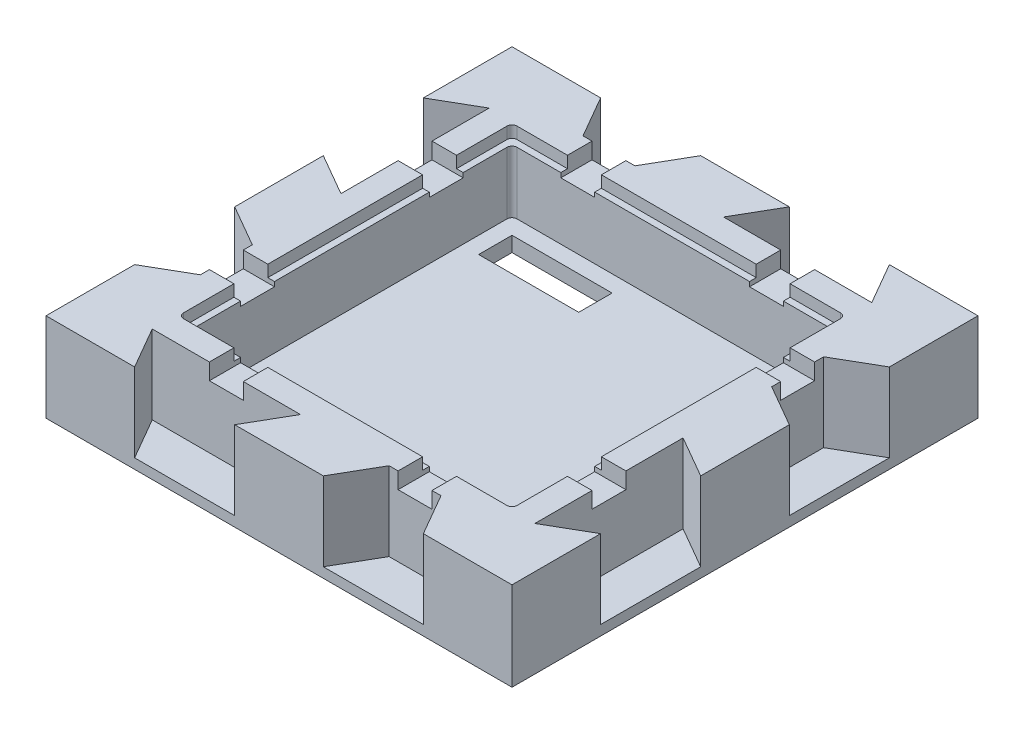
SolidWorks part; units mm, degrees
material "Macor"
ref_plane "Front Plane" through (0, 0, 0) normal (0, 0, 1) x (1, 0, 0)
ref_plane "Top Plane" through (0, 0, 0) normal (0, 1, 0) x (1, 0, 0)
ref_plane "Right Plane" through (0, 0, 0) normal (1, 0, 0) x (0, 0, -1)
sketch "Sketch1" plane through (0, 0, 0) normal (0, 1, 0) x (1, 0, 0)
  line L1 (-69.85, -69.85) -> (69.85, -69.85)
  line L2 (-69.85, -69.85) -> (-69.85, 69.85)
  line L3 (-69.85, 69.85) -> (69.85, 69.85)
  line L4 (69.85, -69.85) -> (69.85, 69.85)
  line L5 (-69.85, -69.85) -> (69.85, 69.85) construction
  line L6 (-69.85, 69.85) -> (69.85, -69.85) construction
  point P0 (0, 0)
  dimension "D1" = 139.7
extrude "Boss-Extrude1" add sketch "Sketch1" along normal mid plane 26.9 contours L2 L1 L4 L3
sketch "Sketch2" plane through (0, 13.45, 0) normal (0, 1, 0) x (1, 0, 0)
  line L0 (69.85, -69.85) -> (69.85, 69.85) construction
  line L1 (-69.85, -69.85) -> (69.85, -69.85)
  line L2 (-69.85, -69.85) -> (-69.85, 69.85)
  line L3 (-69.85, 69.85) -> (69.85, 69.85)
  line L4 (69.85, -69.85) -> (69.85, 69.85)
  line L5 (-69.85, -69.85) -> (69.85, 69.85) construction
  line L6 (-69.85, 69.85) -> (69.85, -69.85) construction
  point P0 (0, 0)
  dimension "D1" = 0
extrude "Cut-Extrude1" cut sketch "Sketch2" against normal offset from surface (0.3 mm away) 0.3 up to face at (0, 13.45, 0)
sketch "Sketch4" plane through (0, 13.15, 0) normal (0, 1, 0) x (1, 0, 0)
  line L0 (-43.2833, -69.85) -> (-50.5002, -57.35)
  line L2 (-50.5002, -57.35) -> (-6.0665, -57.35)
  line L3 (-6.0665, -57.35) -> (-13.2833, -69.85)
  line L4 (-13.2833, -69.85) -> (-43.2833, -69.85)
  line L5 (43.2833, -69.85) -> (36.0665, -57.35)
  line L24 (43.2833, -69.85) -> (13.2833, -69.85)
  line L25 (-69.85, -69.85) -> (-43.2833, -69.85) construction
  line L26 (-13.2833, -69.85) -> (13.2833, -69.85) construction
  line L27 (43.2833, -69.85) -> (69.85, -69.85) construction
  line L28 (36.0665, -57.35) -> (20.5002, -57.35)
  line L30 (13.2833, -69.85) -> (20.5002, -57.35)
  line L31 (-69.85, 69.85) -> (-69.85, -69.85) construction
  line L32 (69.85, -69.85) -> (69.85, 69.85) construction
  line L33 (-69.85, -69.85) -> (69.85, -69.85) construction
  dimension "D2" = 30
  dimension "D1" = 60
  dimension "D3" = 12.5
  dimension "D4" = 60
extrude "Cut-Extrude2" cut sketch "Sketch4" against normal offset from surface 3 and the other way through all up to face at (0, -13.45, 0)
sketch "Sketch18" plane through (0, 0, 57.35) normal (0, 0, 1) x (1, 0, 0)
  line L1 (0, -55) -> (0, 55) construction
  line L3 (23.2033, 13.15) -> (23.2033, 8.275)
  line L4 (23.2033, 8.275) -> (33.3633, 8.275)
  line L5 (33.3633, 13.15) -> (33.3633, 8.275)
  line L6 (-23.2033, 13.15) -> (-33.3633, 13.15)
  line L7 (-33.3633, 13.15) -> (-33.3633, 8.275)
  line L8 (-23.2033, 13.15) -> (-23.2033, 8.275)
  line L9 (-23.2033, 8.275) -> (-33.3633, 8.275)
  line L10 (23.2033, 13.15) -> (33.3633, 13.15)
  line L11 (20.5002, 13.15) -> (36.0665, 13.15) construction
  point P7 (28.2833, 13.15)
  point P14 (28.2833, 13.15)
  dimension "D1" = 10.16
  dimension "D2" = 4.875
extrude "Cut-Extrude6" cut sketch "Sketch18" against normal blind 20
ref_axis "Axis1" through (0, 29.6009, 0) along (0, -1, 0)
pattern_circular "CirPattern1" count 4 over 360 about axis through (0, 29.6009, 0) along (0, -1, 0) of "Cut-Extrude2", "Cut-Extrude6"
sketch "Sketch19" plane through (0, 13.15, 0) normal (0, 1, 0) x (1, 0, 0)
  line L1 (-50, -50) -> (50, -50)
  line L2 (-50, -50) -> (-50, 50)
  line L3 (-50, 50) -> (50, 50)
  line L4 (50, -50) -> (50, 50)
  line L5 (-50, -50) -> (50, 50) construction
  line L6 (-50, 50) -> (50, -50) construction
  point P0 (0, 0)
  dimension "D1" = 100
extrude "Cut-Extrude8" cut sketch "Sketch19" against normal blind 3.5
sketch "Sketch20" plane through (0, 9.65, 0) normal (0, 1, 0) x (1, 0, 0)
  line L1 (-48, -48) -> (48, -48)
  line L2 (-48, -48) -> (-48, 48)
  line L3 (-48, 48) -> (48, 48)
  line L4 (48, -48) -> (48, 48)
  line L5 (-48, -48) -> (48, 48) construction
  line L6 (-48, 48) -> (48, -48) construction
  point P0 (0, 0)
  dimension "D1" = 96
extrude "Cut-Extrude9" cut sketch "Sketch20" against normal blind 18.6
sketch "Sketch21" plane through (0, -8.95, 0) normal (0, 1, 0) x (1, 0, 0)
  line L0 (-48, 48) -> (-48, -48) construction
  line L1 (-13, 33) -> (-43, 33)
  line L2 (-13, 33) -> (-13, 43)
  line L3 (-13, 43) -> (-43, 43)
  line L4 (-43, 33) -> (-43, 43)
  line L5 (48, 48) -> (-48, 48) construction
  dimension "D1" = 30
  dimension "D2" = 10
  dimension "D3" = 5
  dimension "D4" = 5
extrude "Cut-Extrude10" cut sketch "Sketch21" against normal through all
fillet "Fillet2" radius 1.5 8 edges at (-50, 11.4, -50) (-50, 11.4, 50) (50, 11.4, 50) (50, 11.4, -50) (48, 0.35, 48) (-48, 0.35, 48) (-48, 0.35, -48) (48, 0.35, -48)
pattern_circular "CirPattern2" count 2 over 360 about axis through (0, 29.6009, 0) along (0, -1, 0) of "Cut-Extrude10"
sketch "Sketch22" plane through (0, -13.45, 0) normal (0, -1, 0) x (1, 0, 0)
  circle A0 centre (0, 0) radius 25
  dimension "D1" = 50
split line "Split Line1"
equation "\"panel_width\"= 5.5in"
equation "\"finger_joint_width\"= 30mm"
equation "\"D1@Sketch1\"=\"panel_width\""
equation "\"D2@Sketch4\"=\"finger_joint_width\""
